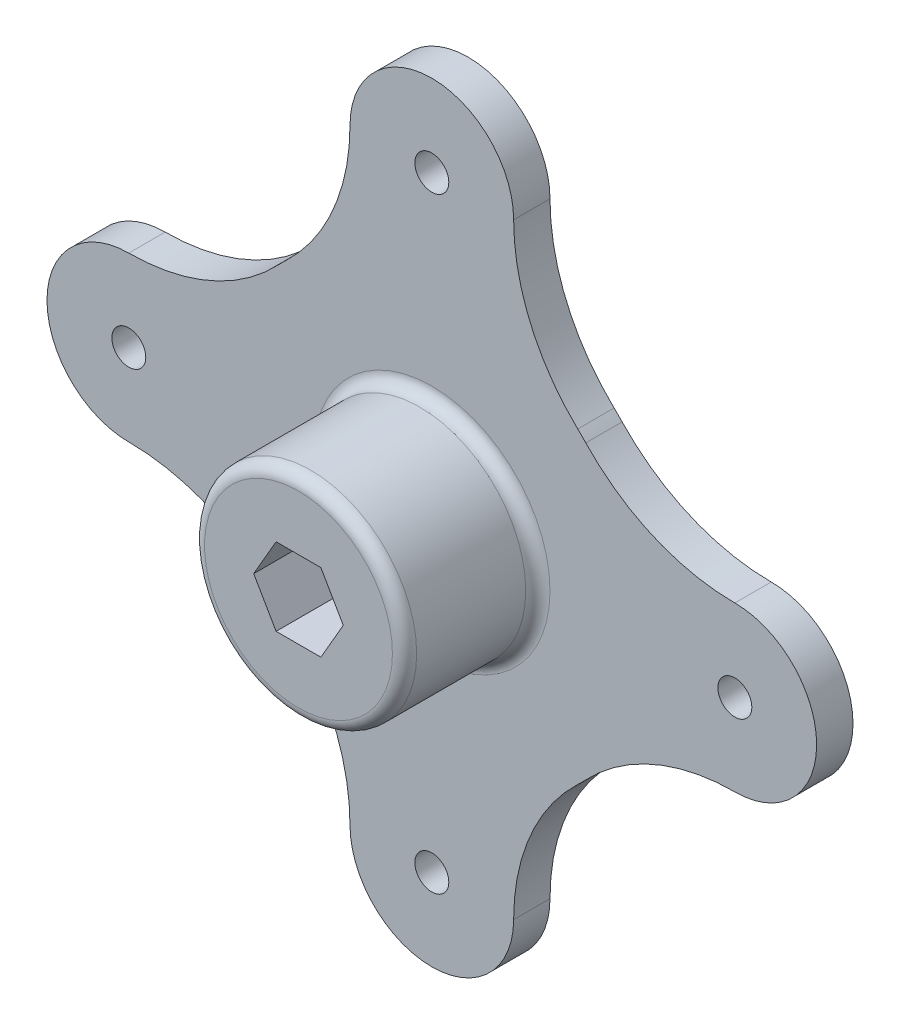
SolidWorks part; units mm, degrees
ref_plane "Front Plane" through (0, 0, 0) normal (0, 0, 1) x (1, 0, 0)
ref_plane "Top Plane" through (0, 0, 0) normal (0, 1, 0) x (1, 0, 0)
ref_plane "Right Plane" through (0, 0, 0) normal (1, 0, 0) x (0, 0, -1)
sketch "Sketch1" plane through (0, 0, 0) normal (0, 0, 1) x (1, 0, 0)
  line L1 (3.695, 0) -> (1.8475, 3.2)
  line L2 (1.8475, 3.2) -> (-1.8475, 3.2)
  line L3 (-1.8475, 3.2) -> (-3.695, 0)
  line L4 (-3.695, 0) -> (-1.8475, -3.2)
  line L5 (-1.8475, -3.2) -> (1.8475, -3.2)
  line L6 (1.8475, -3.2) -> (3.695, 0)
  circle A0 centre (0, 0) radius 3.2 construction
  point P1 (0, 0)
  dimension "D1" = 6.4
sketch "Sketch2" plane through (0, 0, 0) normal (0, 0, 1) x (1, 0, 0)
  circle A0 centre (0, 0) radius 8.75
  point P3 (5.8795, 0)
  dimension "D1" = 17.5
extrude "Boss-Extrude1" add sketch "Sketch2" along normal blind 14
sketch "Sketch3" plane through (0, 0, 0) normal (0, 0, 1) x (1, 0, 0)
  circle A0 centre (0, 25) radius 1.4
  arc A1 (6.75, 25) -> (-6.75, 25) centre (0, 25) ccw
  circle A2 centre (0, 0) radius 17.5 construction
  arc A3 (-6.75, 25) -> (-12.0384, 12.7015) centre (-23.6948, 25) cw
  arc A4 (6.75, 25) -> (12.0384, 12.7015) centre (23.6948, 25) ccw
  arc A5 (-6.75, 25) -> (6.75, 25) centre (0, 25) ccw construction
  arc A6 (-25, 6.75) -> (-12.7015, 12.0384) centre (-25, 23.6948) ccw
  circle A7 centre (-25, 0) radius 1.4
  arc A8 (-25, 6.75) -> (-25, -6.75) centre (-25, 0) ccw
  arc A9 (-25, -6.75) -> (-12.7015, -12.0384) centre (-25, -23.6948) cw
  arc A10 (-6.75, -25) -> (-12.0384, -12.7015) centre (-23.6948, -25) ccw
  circle A11 centre (0, -25) radius 1.4
  arc A12 (-6.75, -25) -> (6.75, -25) centre (0, -25) ccw
  arc A13 (6.75, -25) -> (12.0384, -12.7015) centre (23.6948, -25) cw
  arc A14 (25, -6.75) -> (12.7015, -12.0384) centre (25, -23.6948) ccw
  circle A15 centre (25, 0) radius 1.4
  arc A16 (25, -6.75) -> (25, 6.75) centre (25, 0) ccw
  arc A17 (25, 6.75) -> (12.7015, 12.0384) centre (25, 23.6948) cw
  arc A18 (-12.7015, 12.0384) -> (-12.0384, 12.7015) centre (0, 0) cw
  arc A19 (12.0384, 12.7015) -> (12.7015, 12.0384) centre (0, 0) cw
  arc A20 (12.7015, -12.0384) -> (12.0384, -12.7015) centre (0, 0) cw
  arc A21 (-12.0384, -12.7015) -> (-12.7015, -12.0384) centre (0, 0) cw
  point P38 (0, 0)
  dimension "D1" = 35
  dimension "D2" = 13.5
  dimension "D4" = 2.8
  dimension "D3" = 25
  dimension "D5" = 4
extrude "Boss-Extrude2" add sketch "Sketch3" along normal blind 3 contours A21 A10 A12 A13 A20 A14 A16 A17 A19 A4 A1 A3 A18 A6 A8 A9 A15 A11 A7 A0 region at (0, 0, 0)
fillet "Fillet1" radius 1 2 edges at (8.75, 0, 3) (8.75, 0, 14)
extrude "Cut-Extrude2" cut sketch "Sketch1" along normal up to next
